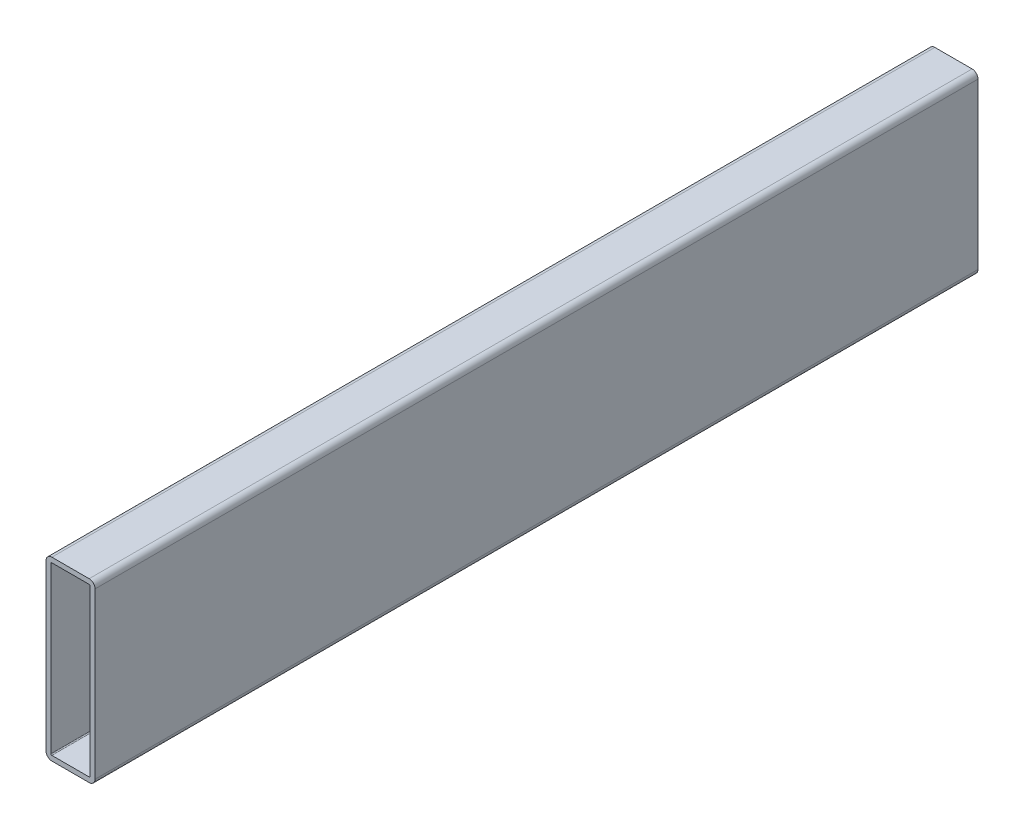
SolidWorks part; units mm, degrees
ref_plane "Front Plane" through (0, 0, 0) normal (0, 0, 1) x (1, 0, 0)
ref_plane "Top Plane" through (0, 0, 0) normal (0, 1, 0) x (1, 0, 0)
ref_plane "Right Plane" through (0, 0, 0) normal (1, 0, 0) x (0, 0, -1)
sketch "Sketch1" plane through (0, 0, 0) normal (0, 0, 1) x (1, 0, 0)
  line L0 (19, 85) -> (-19, 85)
  line L1 (19, -90) -> (-19, -90)
  line L2 (25, -84) -> (25, 84)
  line L3 (19, 90) -> (-19, 90)
  line L4 (-25, -84) -> (-25, 84)
  line L5 (25, -90) -> (-25, 90) construction
  line L6 (25, 90) -> (-25, -90) construction
  line L7 (-20, -84) -> (-20, 84)
  line L8 (19, -85) -> (-19, -85)
  line L9 (20, -84) -> (20, 84)
  arc A0 (-19, -90) -> (-25, -84) centre (-19, -84) cw
  arc A1 (19, -90) -> (25, -84) centre (19, -84) ccw
  arc A2 (25, 84) -> (19, 90) centre (19, 84) ccw
  arc A3 (-19, 90) -> (-25, 84) centre (-19, 84) ccw
  arc A4 (-19, 85) -> (-20, 84) centre (-19, 84) ccw
  arc A5 (-19, -85) -> (-20, -84) centre (-19, -84) cw
  arc A6 (19, -85) -> (20, -84) centre (19, -84) ccw
  arc A7 (20, 84) -> (19, 85) centre (19, 84) ccw
  point P0 (0, 0)
  dimension "D1" = 6
  dimension "D3" = 180
  dimension "D4" = 50
  dimension "D2" = 5
extrude "Boss-Extrude1" add sketch "Sketch1" along normal mid plane 900
equation "\"M5_tap\"=4.2mm"
equation "\"M5_clearence\"=5.5mm"
equation "\"M6_tap\"=5mm"
equation "\"M6_clearence\"=6.6mm"
equation "\"work_area_width\"=1100mm"
equation "\"work_area_depth\"=900mm"
equation "\"D3@Sketch1\"=\"steel_sides_width\""
equation "\"D4@Sketch1\"=\"steel_sides_height\""
equation "\"D1@Sketch1\"=\"steel_sides_radius\""
equation "\"D2@Sketch1\"=\"steel_sides_wall_thickness\""
equation "\"D1@Boss-Extrude1\"=\"work_area_depth\""
equation "\"steel_base_width\"=80mm"
equation "\"steel_base_height\"=50mm"
equation "\"steel_base_wall_thickness\"=3mm"
equation "\"steel_base_radius\"=6mm"
equation "\"steel_sides_width\"=180mm"
equation "\"steel_sides_height\"=50mm"
equation "\"steel_sides_wall_thickness\"=5mm"
equation "\"steel_sides_radius\"=6mm"
equation "\"steel_gantry_width\"=120mm"
equation "\"steel_gantry_height\"=80mm"
equation "\"steel_gantry_wall_thickness\"=6mm"
equation "\"steel_gantry_radius\"=6mm"
